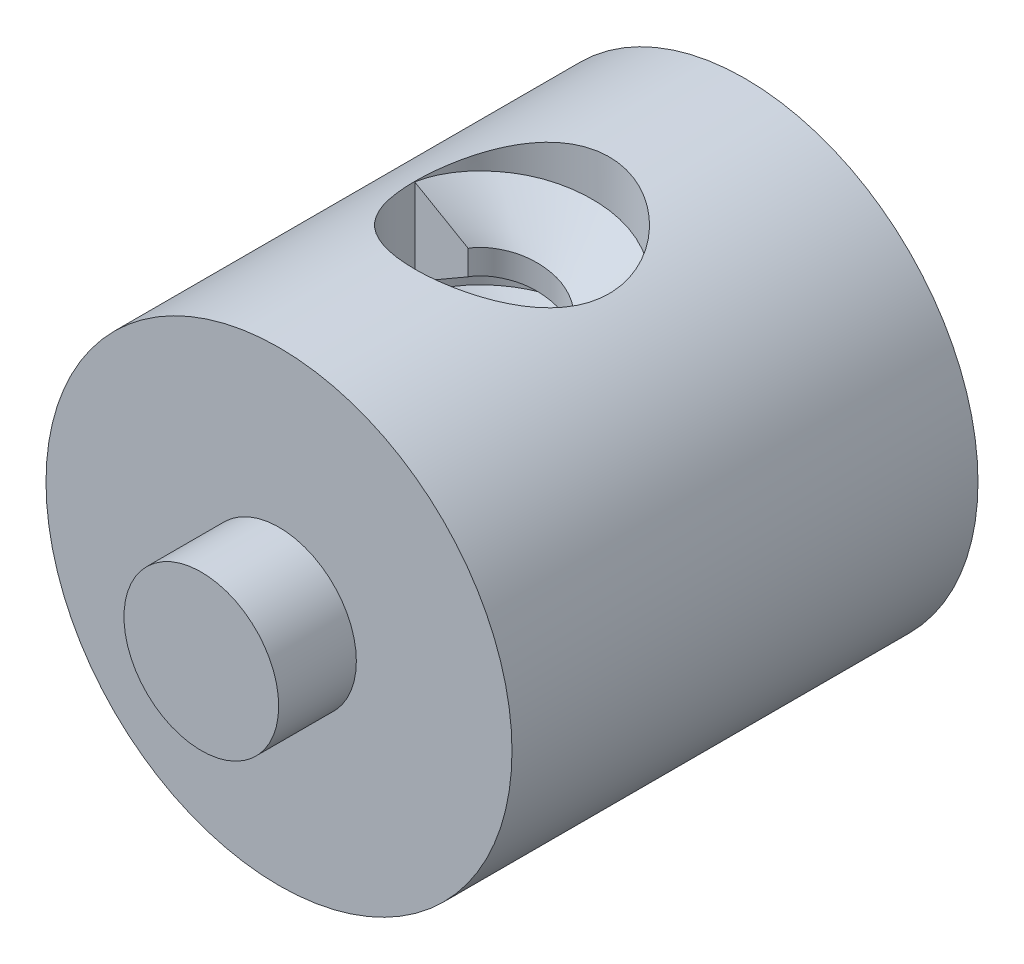
SolidWorks part; units mm, degrees
material "1023 Carbon Steel Sheet (SS)"
ref_plane "Front Plane" through (0, 0, 0) normal (0, 0, 1) x (1, 0, 0)
ref_plane "Top Plane" through (0, 0, 0) normal (0, 1, 0) x (1, 0, 0)
ref_plane "Right Plane" through (0, 0, 0) normal (1, 0, 0) x (0, 0, -1)
sketch "Sketch2" plane through (0, 0, 0) normal (0, 0, 1) x (1, 0, 0)
  circle A0 centre (0, 0) radius 3.75
  dimension "D1" = 7.5
extrude "Boss-Extrude1" add sketch "Sketch2" along normal mid plane 7.5
sketch "Sketch3" plane through (0, 0, 3.75) normal (0, 0, 1) x (1, 0, 0)
  circle A0 centre (0, 0) radius 1.245
  dimension "D1" = 2.49
extrude "Boss-Extrude3" add sketch "Sketch3" along normal blind 1.25 contours A0
mirror "Mirror1" about plane through (0, 0, 0) normal (0, 0, 1) of "Boss-Extrude3"
sketch "Sketch4" plane through (0, 0, 0) normal (0, 1, 0) x (1, 0, 0)
  circle A0 centre (0, 0) radius 1.565
  dimension "D1" = 3.13
extrude "Cut-Extrude2" cut sketch "Sketch4" against normal through all both and the other way through all
sketch "Sketch5" plane through (0, 0, 0) normal (0, 1, 0) x (1, 0, 0)
  point P0 (0, 0)
  point P1 (0, 0)
ref_plane "Plane3" through (0, 3.4, 0) normal (0, 1, 0) x (1, 0, 0)
sketch "Sketch12" plane through (0, 3.4, 0) normal (0, 1, 0) x (1, 0, 0)
  circle A0 centre (0, 0) radius 1.565 construction
  point P0 (1.565, 0)
thread "Thread2" pitch 1.5875 method extrude profile "Thread Profile3" start angle 0, offset 0, length 5.4, pitch 1.5875, diameter 3.13
ref_plane "Plane4" through (-1.565, 3.4, 0) normal (0, 0, 1) x (-1, 0, 0)
sketch "Thread Profile3" plane through (-1.565, 3.4, 0) normal (0, 0, 1) x (-1, 0, 0)
  line L0 (0, 0) -> (0, 1.5875) construction
  line L11 (0, 0) -> (0, 1.3891)
  line L12 (0, 1.3891) -> (-0.8593, 0.893)
  line L13 (-0.8593, 0.893) -> (-0.8593, 0.4961)
  line L15 (-0.8593, 0.4961) -> (0, 0)
  line L17 (-0.8593, 0.6945) -> (0, 0.6945) construction
  point P2 (0, 0)
  dimension "Pitch" = 1.5875
  dimension "Profile_Angle" = 60
  dimension "Profile_Land" = 0.3969
  dimension "Profile_Height" = 0.8593
